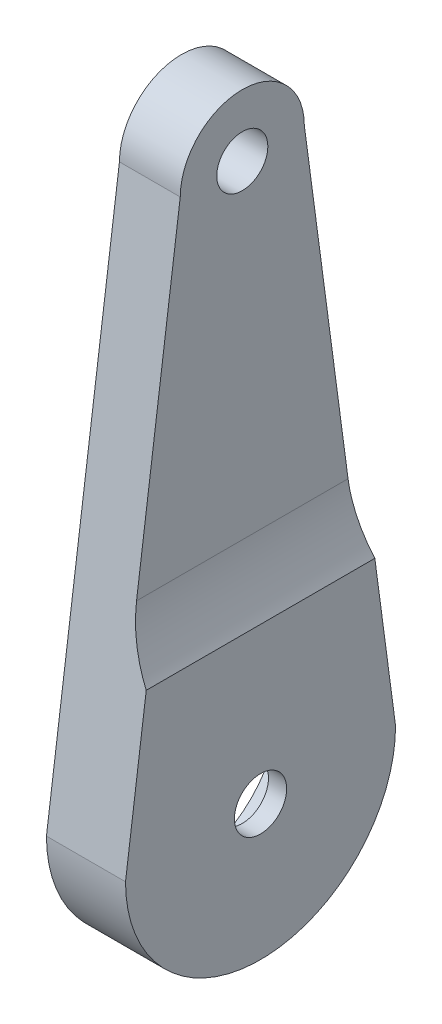
SolidWorks part; units mm, degrees
ref_plane "Front Plane" through (0, 0, 0) normal (1, 0, 0) x (0, 1, 0)
ref_plane "Top Plane" through (0, 0, 0) normal (0, 0, 1) x (0, 1, 0)
ref_plane "Right Plane" through (0, 0, 0) normal (0, 1, 0) x (-1, 0, 0)
sketch "Sketch2" plane through (0, 0, 0) normal (1, 0, 0) x (0, 1, 0)
  line L0 (0, 0) -> (8.1, 0)
  line L3 (42.9, 0) -> (45, 0)
  line L4 (0, 11.1) -> (45, 5.1)
  line L5 (45, -5.1) -> (0, -11.1)
  circle A0 centre (0, 0) radius 8.1
  circle A1 centre (45, 0) radius 2.1
  arc A2 (0, 11.1) -> (0, -11.1) centre (0, 0) ccw
  arc A3 (45, -5.1) -> (45, 5.1) centre (45, 0) ccw
  circle A4 centre (0, 0) radius 11.1 construction
  circle A5 centre (45, 0) radius 5.1 construction
  dimension "D1" = 16.2
  dimension "D2" = 4.2
  dimension "D4" = 3
  dimension "D3" = 3
extrude "Boss-Extrude1" add sketch "Sketch2" along normal mid plane 5 contours L5 A3 L4 A2 A0 A1 region at (0, 19.8667, 0)
sketch "Sketch3" plane through (-2.5, 0, 0) normal (1, 0, 0) x (0, 1, 0)
  circle A0 centre (0, 0) radius 4.25
  dimension "D1" = 8.5
extrude "Cut-Extrude1" [suppressed] cut sketch "Sketch3" along normal blind 0.8
sketch "Sketch5" plane through (2.5, 0, 0) normal (1, 0, 0) x (0, 1, 0)
  line L3 (12.7776, 9.3963) -> (12.7776, -9.3963)
  line L4 (0, 11.1) -> (45, 5.1) construction
  line L5 (45, -5.1) -> (0, -11.1) construction
  line L6 (12.7776, -9.3963) -> (0, -11.1)
  line L7 (0, 11.1) -> (12.7776, 9.3963)
  arc A2 (0, 11.1) -> (0, -11.1) centre (0, 0) ccw construction
  arc A3 (0, 11.1) -> (0, -11.1) centre (0, 0) ccw
  circle A4 centre (0, 0) radius 2.15
  dimension "D1" = 4.3
extrude "Boss-Extrude3" add sketch "Sketch5" along normal blind 1.5
fillet "Fillet2" radius 10 1 edges at (2.5, 12.7776, 0)
